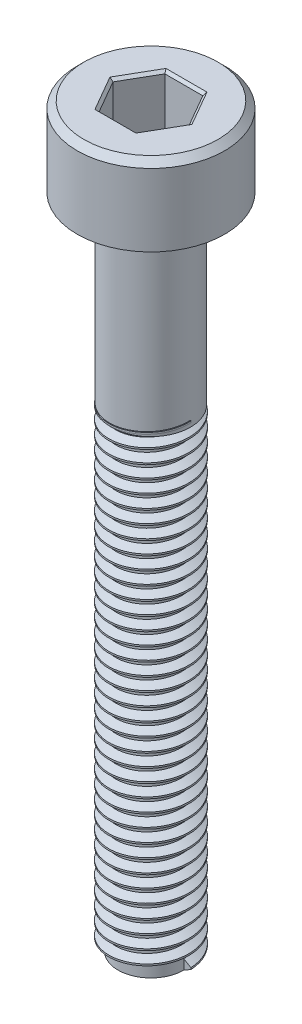
SolidWorks part; units mm, degrees
ref_plane "Front Plane" through (0, 0, 0) normal (0, 0, 1) x (1, 0, 0)
ref_plane "Top Plane" through (0, 0, 0) normal (0, 1, 0) x (1, 0, 0)
ref_plane "Right Plane" through (0, 0, 0) normal (1, 0, 0) x (0, 0, -1)
sketch "Sketch1" plane through (0, 0, 0) normal (0, 1, 0) x (1, 0, 0)
  circle A0 centre (0, 0) radius 1.5
  dimension "D1" = 3
extrude "Boss-Extrude1" add sketch "Sketch1" against normal blind 7
sketch "Sketch2" plane through (0, -7, 0) normal (0, -1, 0) x (1, 0, 0)
  circle A0 centre (0, 0) radius 1.25
  dimension "D1" = 2.5
extrude "Boss-Extrude2" add sketch "Sketch2" along normal blind 18
thread "Thread1" pitch 0.5 method extrude profile "Thread Profile1" start angle 0, offset 0, length 0, pitch 0.5, diameter 2.5
ref_plane "Plane1" through (1.25, -25, 0) normal (0, 0, 1) x (1, 0, 0)
sketch "Thread Profile1" plane through (1.25, -25, 0) normal (0, 0, 1) x (1, 0, 0)
  line L0 (0, 0) -> (0, 0.5) construction
  line L1 (0, 0) -> (0.2706, 0.1562)
  line L2 (0.2706, 0.1562) -> (0.2706, 0.2187)
  line L3 (0.2706, 0.2187) -> (0, 0.375)
  line L4 (0.2706, 0.1875) -> (0, 0.1875) construction
  line L11 (0, 0) -> (0, 0.375)
  point P2 (0, 0)
  dimension "Pitch" = 0.5
  dimension "Profile_Angle" = 60
  dimension "Profile_Land" = 0.0625
  dimension "Profile_Height" = 0.2706
sketch "Sketch5" plane through (0, 0, 0) normal (0, 1, 0) x (1, 0, 0)
  circle A0 centre (0, 0) radius 2.8
  dimension "D1" = 5.6
extrude "Boss-Extrude3" add sketch "Sketch5" along normal blind 3
sketch "Sketch6" plane through (0, 3, 0) normal (0, 1, 0) x (1, 0, 0)
  line L1 (1.4434, 0) -> (0.7217, 1.25)
  line L2 (0.7217, 1.25) -> (-0.7217, 1.25)
  line L3 (-0.7217, 1.25) -> (-1.4434, 0)
  line L4 (-1.4434, 0) -> (-0.7217, -1.25)
  line L5 (-0.7217, -1.25) -> (0.7217, -1.25)
  line L6 (0.7217, -1.25) -> (1.4434, 0)
  circle A0 centre (0, 0) radius 1.25 construction
  dimension "D1" = 2.5
  dimension "D2" = 1.25
extrude "Cut-Extrude1" cut sketch "Sketch6" against normal blind 2
chamfer "Chamfer1" distance 0.1 angle 45 6 edges at (-1.0825, 3, 0.625) (0, 3, 1.25) (1.0825, 3, 0.625) (1.0825, 3, -0.625) (-1.0825, 3, -0.625) (0, 3, -1.25)
chamfer "Chamfer2" distance 0.25 angle 45 1 edges at (0, 3, 2.8)
